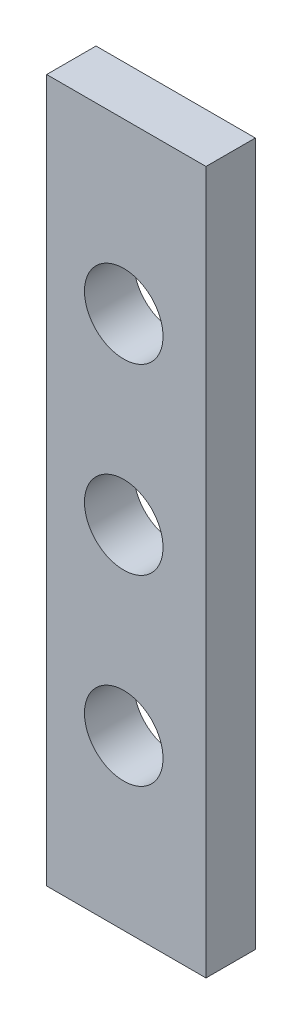
SolidWorks part; units mm, degrees
ref_plane "前视基准面" through (0, 0, 0) normal (0, 0, 1) x (1, 0, 0)
ref_plane "上视基准面" through (0, 0, 0) normal (0, 1, 0) x (1, 0, 0)
ref_plane "右视基准面" through (0, 0, 0) normal (1, 0, 0) x (0, 0, -1)
sketch "草图1" plane through (0, 0, 0) normal (0, 0, 1) x (1, 0, 0)
  line L6 (-130, -105) -> (-121.2816, -105)
  line L7 (-130, -105) -> (-130, -66.5374)
  line L8 (-130, -66.5374) -> (-121.2816, -66.5374)
  line L9 (-121.2816, -105) -> (-121.2816, -66.5374)
  point P1 (0, 0)
  point P5 (0, 0)
extrude "凸台-拉伸1" add sketch "草图1" along normal blind 2.7
hole_wizard "打孔尺寸(%根据十字)槽沉头木螺钉的类型1" positions "草图2" profile "草图3" countersink size "M4" standard "GB"
sketch "草图2" plane through (40.4914, -131.0101, 7) normal (0, 0, 1) x (0, 1, 0)
  point P0 (35.2414, 166.273)
  point P3 (45.2414, 166.273)
  point P6 (55.2414, 166.273)
  point P9 (206.7788, 166.273)
  point P12 (216.7788, 166.273)
  point P15 (226.7788, 166.273)
sketch "草图3" plane through (-125.7816, -95.7687, 7) normal (1, 0, 0) x (0, -1, 0)
  line L0 (0, 0) -> (0, 20.2919)
  line L1 (0, 20.2919) -> (2.15, 19)
  line L2 (2.15, 19) -> (2.15, 1.85)
  line L3 (2.15, 1.85) -> (4, 0)
  line L4 (4, 0) -> (0, 0)
  line L5 (-2.15, 1.85) -> (-4, 0) construction
  line L6 (0, 20.2919) -> (-2.15, 19) construction
  line L7 (0, -6.35) -> (0, 107.95) construction
  dimension "孔直径" = 4.3
  dimension "孔深度" = 19
  dimension "近端锥形沉头孔直径" = 8
  dimension "近端锥形沉头孔角度" = 90
  dimension "导头角度" = 118
